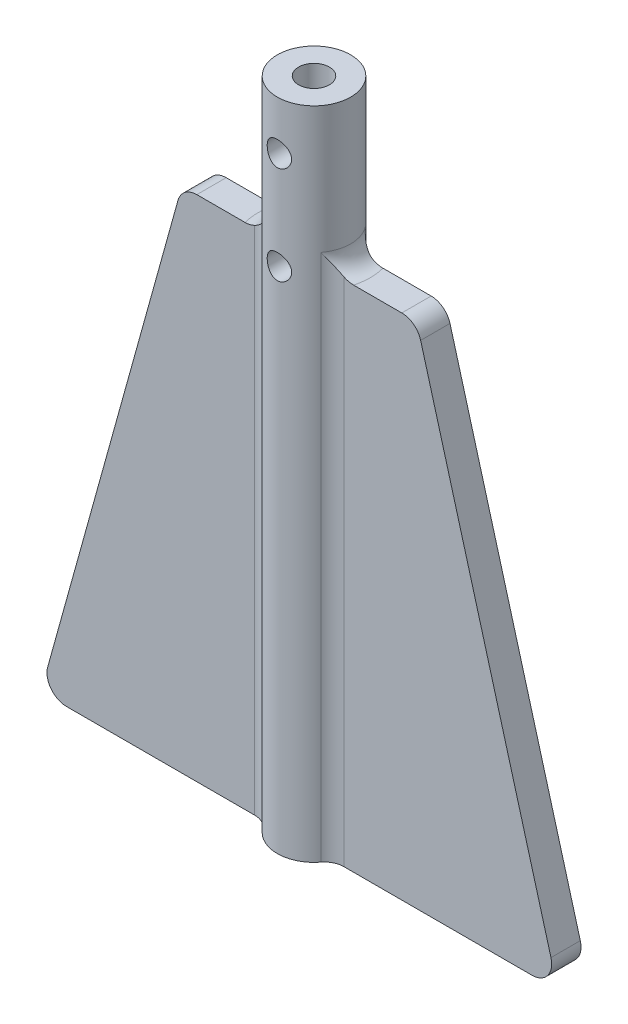
SolidWorks part; units mm, degrees
ref_plane "Front Plane" through (0, 0, 0) normal (0, 0, 1) x (1, 0, 0)
ref_plane "Top Plane" through (0, 0, 0) normal (0, 1, 0) x (1, 0, 0)
ref_plane "Right Plane" through (0, 0, 0) normal (1, 0, 0) x (0, 0, -1)
sketch "Sketch1" plane through (0, 0, 0) normal (0, 1, 0) x (1, 0, 0)
  circle A0 centre (0, 0) radius 3.75
  dimension "D1" = 7.5
extrude "Boss-Extrude1" add sketch "Sketch1" along normal blind 15
sketch "Sketch2" plane through (0, 0, 0) normal (0, -1, 0) x (1, 0, 0)
  line L0 (-3.4369, 1.5) -> (-12, 1.5)
  line L1 (-12, 1.5) -> (-12, -1.5)
  line L2 (-12, -1.5) -> (-3.4369, -1.5)
  line L3 (3.4369, -1.5) -> (12, -1.5)
  line L4 (12, -1.5) -> (12, 1.5)
  line L5 (12, 1.5) -> (3.4369, 1.5)
  arc A1 (-3.4369, -1.5) -> (3.4369, -1.5) centre (0, 0) ccw
  arc A2 (3.4369, 1.5) -> (-3.4369, 1.5) centre (0, 0) ccw
  circle A3 centre (0, 0) radius 3.75 construction
  point P0 (-3.4369, 1.5)
  point P1 (3.4369, 1.5)
  point P4 (3.4369, -1.5)
  point P5 (-3.4369, -1.5)
  dimension "D1" = 3
  dimension "D2" = 24
ref_plane "Plane1" through (0, -52, 0) normal (0, 1, 0) x (1, 0, 0)
sketch "Sketch3" plane through (0, -52, 0) normal (0, 1, 0) x (1, 0, 0)
  line L0 (-3.4369, 1.5) -> (-26.4369, 1.5)
  line L1 (-26.4369, 1.5) -> (-26.4369, -1.5)
  line L2 (-26.4369, -1.5) -> (-3.4369, -1.5)
  line L3 (3.4369, -1.5) -> (26.4369, -1.5)
  line L4 (26.4369, -1.5) -> (26.4369, 1.5)
  line L5 (26.4369, 1.5) -> (3.4369, 1.5)
  circle A0 centre (0, 0) radius 3.75 construction
  arc A1 (-3.4369, -1.5) -> (3.4369, -1.5) centre (0, 0) ccw
  arc A2 (3.4369, 1.5) -> (-3.4369, 1.5) centre (0, 0) ccw
  dimension "D1" = 23
loft "Loft1" add profiles "Sketch3", "Sketch2" connector at (26.4369, -52, 1.5) connector at (12, 0, 1.5)
fillet "Fillet1" radius 2 6 edges
fillet "Fillet2" radius 2 4 edges
sketch "Sketch4" plane through (0, 15, 0) normal (0, 1, 0) x (1, 0, 0)
  circle A0 centre (0, 0) radius 1.575
  dimension "D1" = 3.15
extrude "Cut-Extrude1" cut sketch "Sketch4" against normal blind 20
ref_plane "Plane2" through (0, 0, 3.75) normal (0, 0, 1) x (1, 0, 0)
sketch "Sketch5" plane through (0, 0, 3.75) normal (0, 0, 1) x (1, 0, 0)
  line L0 (3.75, 15) -> (-3.75, 15) construction
  point P0 (0, 10)
  point P1 (0, 0)
  dimension "D1" = 5
  dimension "D2" = 10
hole_wizard "M3x0.5 Tapped Hole1" positions "Sketch8" profile "Sketch9" tap size "M3x0.5" standard "ANSI Metric"
sketch "Sketch8" plane through (0, 0, 3.75) normal (0, 0, 1) x (1, 0, 0)
  point P0 (0, 10)
  point P3 (0, 0)
sketch "Sketch9" plane through (0, 10, 3.75) normal (1, 0, 0) x (0, -1, 0)
  line L0 (0, 0) -> (0, 3.7511)
  line L1 (0, 3.7511) -> (1.25, 3)
  line L2 (1.25, 3) -> (1.25, 0)
  line L5 (1.25, 0) -> (0, 0)
  line L10 (0, 3.7511) -> (-1.25, 3) construction
  line L11 (0, -6.35) -> (0, 107.95) construction
  dimension "Tap Drill Dia." = 2.5
  dimension "Tap Drill Depth" = 3
  dimension "Drill Angle" = 118
cosmetic thread "Hole Thread3" parameters "D1"=2.8335, "D2"=3
cosmetic thread "Hole Thread4" parameters "D1"=2.8335, "D2"=3
